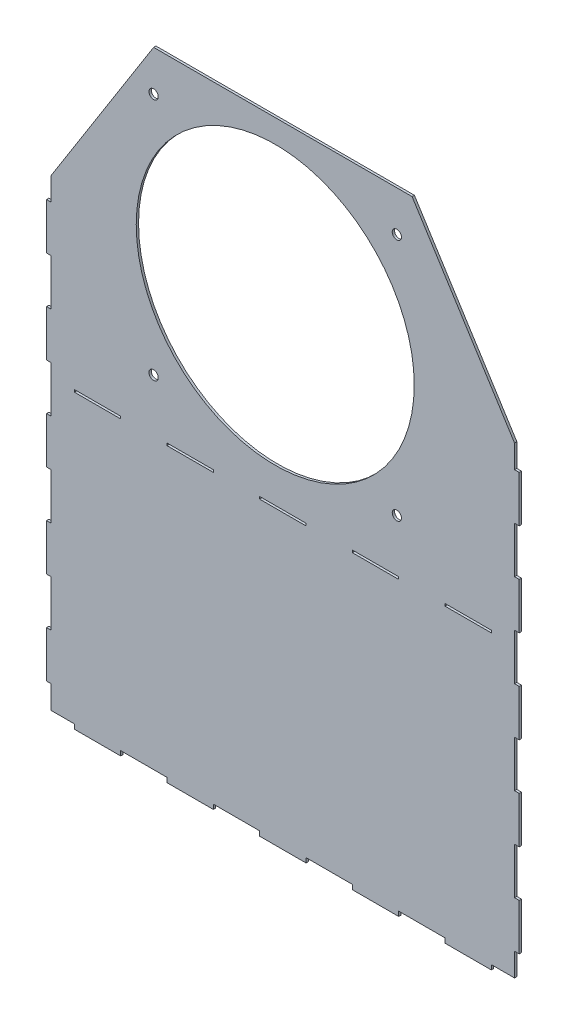
SolidWorks part; units mm, degrees
ref_plane "Přední rovina" through (0, 0, 0) normal (0, 0, 1) x (1, 0, 0)
ref_plane "Horní rovina" through (0, 0, 0) normal (0, 1, 0) x (1, 0, 0)
ref_plane "Pravá rovina" through (0, 0, 0) normal (1, 0, 0) x (0, 0, -1)
sketch "Skica1" plane through (0, 0, 0) normal (0, 0, 1) x (1, 0, 0)
  line L0 (-24.5981, -113.24) -> (-24.5981, -95.4761)
  line L1 (-124.5981, -113.24) -> (75.4019, -113.24)
  line L2 (-124.5981, -113.24) -> (-124.5981, 156.76)
  line L3 (-124.5981, 156.76) -> (75.4019, 156.76)
  line L4 (75.4019, -113.24) -> (75.4019, 156.76)
  line L5 (-114.5981, -113.24) -> (-94.5981, -113.24)
  line L6 (-114.5981, -113.24) -> (-114.5981, -115.24)
  line L7 (-114.5981, -115.24) -> (-94.5981, -115.24)
  line L8 (-94.5981, -113.24) -> (-94.5981, -115.24)
  line L9 (-74.5981, -113.24) -> (-54.5981, -113.24)
  line L10 (-74.5981, -113.24) -> (-74.5981, -115.24)
  line L11 (-74.5981, -115.24) -> (-54.5981, -115.24)
  line L12 (-54.5981, -113.24) -> (-54.5981, -115.24)
  line L13 (-34.5981, -113.24) -> (-14.5981, -113.24)
  line L14 (-34.5981, -113.24) -> (-34.5981, -115.24)
  line L15 (-34.5981, -115.24) -> (-14.5981, -115.24)
  line L16 (-14.5981, -113.24) -> (-14.5981, -115.24)
  line L17 (25.4019, -115.24) -> (5.4019, -115.24)
  line L18 (5.4019, -113.24) -> (5.4019, -115.24)
  line L19 (25.4019, -113.24) -> (5.4019, -113.24)
  line L20 (25.4019, -113.24) -> (25.4019, -115.24)
  line L21 (65.4019, -115.24) -> (45.4019, -115.24)
  line L22 (45.4019, -113.24) -> (45.4019, -115.24)
  line L23 (65.4019, -113.24) -> (45.4019, -113.24)
  line L24 (65.4019, -113.24) -> (65.4019, -115.24)
  line L25 (75.4019, 36.76) -> (77.4019, 36.76)
  line L26 (-124.5981, -103.24) -> (-126.5981, -103.24)
  line L27 (-124.5981, -103.24) -> (-124.5981, -83.24)
  line L28 (-124.5981, -83.24) -> (-126.5981, -83.24)
  line L29 (-126.5981, -103.24) -> (-126.5981, -83.24)
  line L30 (-124.5981, -63.24) -> (-126.5981, -63.24)
  line L31 (-124.5981, -63.24) -> (-124.5981, -43.24)
  line L32 (-124.5981, -43.24) -> (-126.5981, -43.24)
  line L33 (-126.5981, -63.24) -> (-126.5981, -43.24)
  line L34 (-124.5981, -23.24) -> (-126.5981, -23.24)
  line L35 (-124.5981, -23.24) -> (-124.5981, -3.24)
  line L36 (-124.5981, -3.24) -> (-126.5981, -3.24)
  line L37 (-126.5981, -23.24) -> (-126.5981, -3.24)
  line L38 (-124.5981, 16.76) -> (-126.5981, 16.76)
  line L39 (-124.5981, 16.76) -> (-124.5981, 36.76)
  line L40 (-124.5981, 36.76) -> (-126.5981, 36.76)
  line L41 (-126.5981, 16.76) -> (-126.5981, 36.76)
  line L42 (77.4019, 16.76) -> (77.4019, 36.76)
  line L43 (75.4019, 16.76) -> (77.4019, 16.76)
  line L44 (75.4019, 16.76) -> (75.4019, 36.76)
  line L45 (75.4019, -3.24) -> (77.4019, -3.24)
  line L46 (77.4019, -23.24) -> (77.4019, -3.24)
  line L47 (75.4019, -23.24) -> (77.4019, -23.24)
  line L48 (75.4019, -23.24) -> (75.4019, -3.24)
  line L49 (75.4019, -43.24) -> (77.4019, -43.24)
  line L50 (77.4019, -63.24) -> (77.4019, -43.24)
  line L51 (75.4019, -63.24) -> (77.4019, -63.24)
  line L52 (75.4019, -63.24) -> (75.4019, -43.24)
  line L53 (75.4019, -83.24) -> (77.4019, -83.24)
  line L54 (77.4019, -103.24) -> (77.4019, -83.24)
  line L55 (75.4019, -103.24) -> (77.4019, -103.24)
  line L56 (75.4019, -103.24) -> (75.4019, -83.24)
  line L57 (-80.3799, 156.76) -> (-124.5981, 86.76)
  line L58 (-114.5981, 11.76) -> (-94.5981, 11.76)
  line L59 (-114.5981, 11.76) -> (-114.5981, 10.76)
  line L60 (-114.5981, 10.76) -> (-94.5981, 10.76)
  line L61 (-94.5981, 11.76) -> (-94.5981, 10.76)
  line L62 (-74.5981, 11.76) -> (-54.5981, 11.76)
  line L63 (-74.5981, 11.76) -> (-74.5981, 10.76)
  line L64 (-74.5981, 10.76) -> (-54.5981, 10.76)
  line L65 (-54.5981, 11.76) -> (-54.5981, 10.76)
  line L66 (-34.5981, 11.76) -> (-14.5981, 11.76)
  line L67 (-34.5981, 11.76) -> (-34.5981, 10.76)
  line L68 (-34.5981, 10.76) -> (-14.5981, 10.76)
  line L69 (-14.5981, 11.76) -> (-14.5981, 10.76)
  line L70 (5.4019, 11.76) -> (25.4019, 11.76)
  line L71 (5.4019, 11.76) -> (5.4019, 10.76)
  line L72 (5.4019, 10.76) -> (25.4019, 10.76)
  line L73 (25.4019, 11.76) -> (25.4019, 10.76)
  line L74 (45.4019, 11.76) -> (65.4019, 11.76)
  line L75 (45.4019, 11.76) -> (45.4019, 10.76)
  line L76 (45.4019, 10.76) -> (65.4019, 10.76)
  line L77 (65.4019, 11.76) -> (65.4019, 10.76)
  line L78 (-124.5981, 56.76) -> (-126.5981, 56.76)
  line L79 (-124.5981, 56.76) -> (-124.5981, 76.76)
  line L80 (-124.5981, 76.76) -> (-126.5981, 76.76)
  line L81 (-126.5981, 56.76) -> (-126.5981, 76.76)
  line L82 (31.1836, 156.76) -> (75.4019, 86.76)
  line L83 (75.4019, 76.76) -> (77.4019, 76.76)
  line L84 (77.4019, 56.76) -> (77.4019, 76.76)
  line L85 (75.4019, 56.76) -> (77.4019, 56.76)
  line L86 (75.4019, 56.76) -> (75.4019, 76.76)
  circle A0 centre (-27.8799, 86.76) radius 60
  circle A1 centre (-80.3799, 139.26) radius 2
  circle A2 centre (24.6201, 139.26) radius 2
  circle A3 centre (24.6201, 34.26) radius 2
  circle A4 centre (-80.3799, 34.26) radius 2
  point P89 (-124.5981, 86.76)
  point P93 (-80.3799, 156.76)
  dimension "D3" = 120
  dimension "D4" = 70
  dimension "D6" = 4
  dimension "D7" = 4
  dimension "D8" = 4
  dimension "D9" = 4
  dimension "D1" = 270
  dimension "D2" = 200
  dimension "D5" = 105
  dimension "D10" = 105
  dimension "D11" = 52.5
  dimension "D12" = 52.5
  dimension "D13" = 20
  dimension "D14" = 20
  dimension "D15" = 20
  dimension "D16" = 20
  dimension "D17" = 10
  dimension "D18" = 20
  dimension "D19" = 2
  dimension "D20" = 10
  dimension "D21" = 20
  dimension "D22" = 20
  dimension "D23" = 20
  dimension "D24" = 20
  dimension "D25" = 20
  dimension "D26" = 20
  dimension "D27" = 20
  dimension "D28" = 2
  dimension "D29" = 1
  dimension "D30" = 20
  dimension "D31" = 20
  dimension "D32" = 10
  dimension "D33" = 5
extrude "Přidat vysunutím1" add sketch "Skica1" along normal blind 1 contours L8 L1 L6 L7 | L41 L38 L2 L40 | L37 L34 L2 L36 | L1 L4 L3 L2 A4 A3 A2 A1 A0 L58 L61 L60 L59 L62 L65 | L42 L25 L44 L43 | L46 L45 L48 L47 | L50 L49 L52 L51 | L54 L53 L56 L55 | L21 L22 L23 L24 | L17 L18 L19 L20 | L15 L16 L13 L14 | L11 L12 L9 L10 | L29 L28 L27 L26 | L33 L32 L31 L30 | L79 L78 L81 L80 | L83 L84 L85 L86 region at (-23.653, -5.6959, 0) region at (-104.5981, -114.24, 0) region at (-125.5981, -13.24, 0) region at (-125.5981, 26.76, 0)
